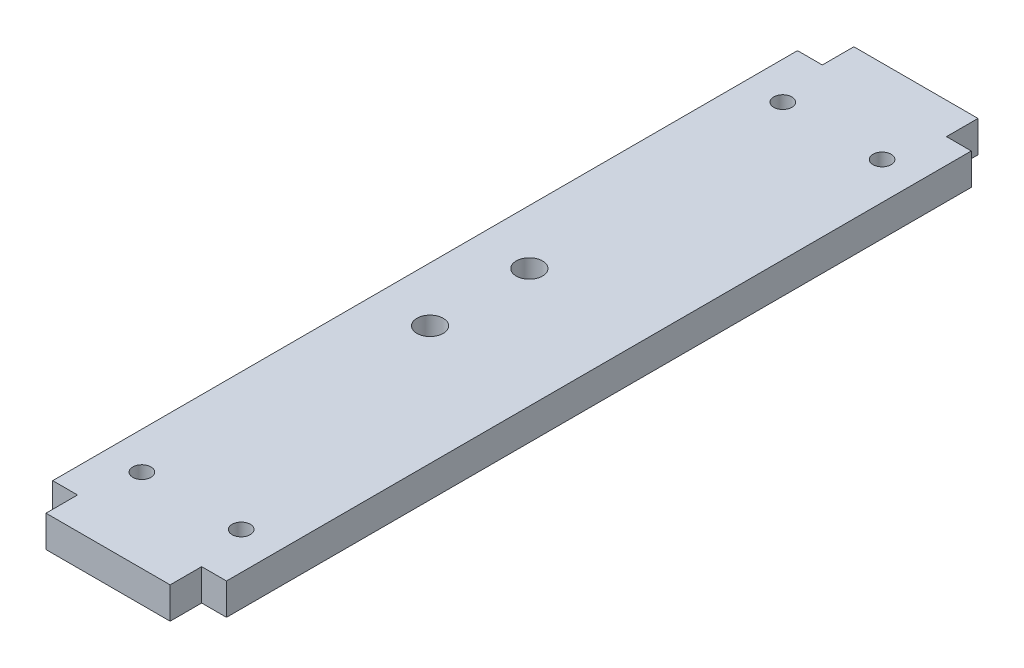
SolidWorks part; units mm, degrees
ref_plane "Front Plane" through (0, 0, 0) normal (0, 0, 1) x (1, 0, 0)
ref_plane "Top Plane" through (0, 0, 0) normal (0, 1, 0) x (1, 0, 0)
ref_plane "Right Plane" through (0, 0, 0) normal (1, 0, 0) x (0, 0, -1)
sketch "Sketch1" plane through (0, 0, 0) normal (0, 1, 0) x (1, 0, 0)
  line L1 (17.5, -75) -> (-17.5, -75)
  line L2 (17.5, -75) -> (17.5, 75)
  line L3 (17.5, 75) -> (-17.5, 75)
  line L4 (-17.5, -75) -> (-17.5, 75)
  line L5 (17.5, -75) -> (-17.5, 75) construction
  line L6 (17.5, 75) -> (-17.5, -75) construction
  point P0 (0, 0)
  dimension "D1" = 150
  dimension "D2" = 35
extrude "Boss-Extrude1" add sketch "Sketch1" along normal blind 6.35
sketch "Sketch2" plane through (0, 6.35, 0) normal (0, 1, 0) x (1, 0, 0)
  line L0 (-17.5, -75) -> (17.5, -75) construction
  line L1 (-12.5, -81.35) -> (12.5, -81.35)
  line L2 (-12.5, -81.35) -> (-12.5, -75)
  line L3 (-12.5, -75) -> (12.5, -75)
  line L4 (12.5, -81.35) -> (12.5, -75)
  line L5 (-12.5, -81.35) -> (12.5, -75) construction
  line L6 (-12.5, -75) -> (12.5, -81.35) construction
  line L7 (17.5, 75) -> (-17.5, 75) construction
  line L8 (-12.5, 81.35) -> (12.5, 81.35)
  line L9 (-12.5, 81.35) -> (-12.5, 75)
  line L10 (-12.5, 75) -> (12.5, 75)
  line L11 (12.5, 81.35) -> (12.5, 75)
  line L12 (-12.5, 81.35) -> (12.5, 75) construction
  line L13 (-12.5, 75) -> (12.5, 81.35) construction
  point P0 (0, -78.175)
  point P7 (0, 78.175)
  point P14 (0, 0)
  dimension "D1" = 25
  dimension "D2" = 6.35
extrude "Boss-Extrude2" add sketch "Sketch2" against normal blind 6.35
sketch "Sketch3" plane through (0, 6.35, 0) normal (0, 1, 0) x (1, 0, 0)
  line L0 (-10, 64.5352) -> (10, 64.5352) construction
  line L1 (-10, -64.5352) -> (10, -64.5352) construction
  line L2 (-12.5, 75) -> (-17.5, 75) construction
  line L3 (-17.5, -75) -> (-12.5, -75) construction
  point P4 (0, 64.5352)
  point P5 (0, -64.5352)
  dimension "D1" = 20
  dimension "D2" = 10.4648
  dimension "D3" = 10.4648
hole_wizard "#6 Clearance Hole1" positions "3DSketch1" profile "Sketch4" hole size "#6" standard "ANSI Inch" end condition through all
sketch3d "3DSketch1"
  point P0 (-10, 6.35, -64.5352)
  point P3 (10, 6.35, -64.5352)
  point P6 (10, 6.35, 64.5352)
  point P9 (-10, 6.35, 64.5352)
sketch "Sketch4" plane through (-10, 6.35, -64.5352) normal (1, 0, 0) x (0, 0, 1)
  line L0 (0, 0) -> (0, 6.35)
  line L1 (0, 6.35) -> (1.8288, 6.35)
  line L2 (1.8288, 6.35) -> (1.8288, 0)
  line L5 (1.8288, 0) -> (0, 0)
  line L11 (0, -6.35) -> (0, 107.95) construction
  dimension "Thru Hole Dia." = 3.6576
  dimension "Thru Hole Depth" = 6.35
sketch "Sketch5" plane through (0, 6.35, 0) normal (0, 1, 0) x (1, 0, 0)
  line L0 (-6.5, 10) -> (-6.5, -10) construction
  point P2 (-6.5, 0)
  dimension "D1" = 20
  dimension "D2" = 6.5
hole_wizard "M5 Clearance Hole1" positions "3DSketch2" profile "Sketch6" hole size "M5" standard "ANSI Metric" end condition through all
sketch3d "3DSketch2"
  point P0 (-6.5, 6.35, 10)
  point P3 (-6.5, 6.35, -10)
sketch "Sketch6" plane through (-6.5, 6.35, 10) normal (1, 0, 0) x (0, 0, 1)
  line L0 (0, 0) -> (0, 6.35)
  line L1 (0, 6.35) -> (2.65, 6.35)
  line L2 (2.65, 6.35) -> (2.65, 0)
  line L5 (2.65, 0) -> (0, 0)
  line L11 (0, -6.35) -> (0, 107.95) construction
  dimension "Thru Hole Dia." = 5.3
  dimension "Thru Hole Depth" = 6.35
